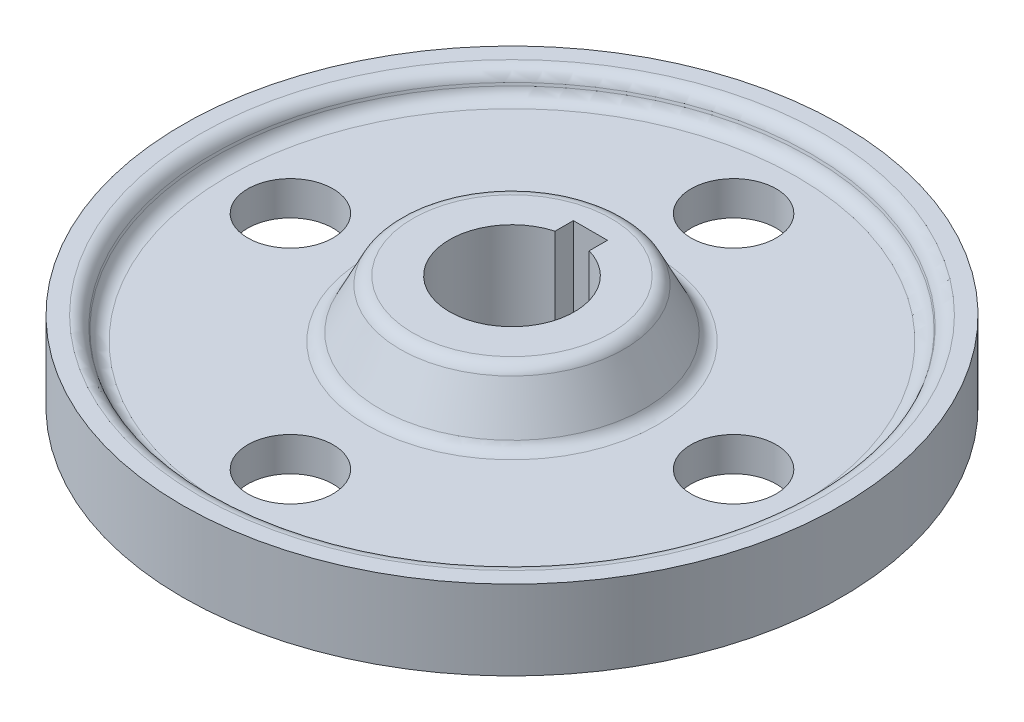
SolidWorks part; units mm, degrees
material "炭素鋼(普通)"
ref_plane "VERT" through (0, 0, 0) normal (0, 0, 1) x (1, 0, 0)
ref_plane "HOR" through (0, 0, 0) normal (0, 1, 0) x (1, 0, 0)
ref_plane "CTR" through (0, 0, 0) normal (1, 0, 0) x (0, 0, -1)
ref_axis "A_X" through (60.9, 0, 0) along (-1, 0, 0)
ref_axis "A_Y" through (0, 14.3, 0) along (0, -1, 0)
ref_axis "A_Z" through (0, 0, 63.8) along (0, 0, -1)
sketch3d "PNT_CG"
  point P0 (0, 0, 0)
sketch "Sketch1" plane through (0, 0, 0) normal (0, 1, 0) x (1, 0, 0)
  circle A0 centre (0, 0) radius 58
  dimension "D1" = 116
extrude "Boss-Extrude1" add sketch "Sketch1" along normal blind 13
sketch "Sketch3" plane through (0, 13, 0) normal (0, 1, 0) x (1, 0, 0)
  circle A0 centre (0, 0) radius 11
  dimension "D1" = 22
extrude "Cut-Extrude1" cut sketch "Sketch3" against normal through all contours A0
sketch "Sketch5" plane through (0, 13, 0) normal (0, 1, 0) x (1, 0, 0)
  circle A0 centre (0, 0) radius 39 construction
  circle A1 centre (0, 39) radius 7.5
  circle A2 centre (39, 0) radius 7.5
  circle A3 centre (0, -39) radius 7.5
  circle A4 centre (-39, 0) radius 7.5
  point P14 (0, 0)
  dimension "D1" = 78
  dimension "D2" = 4
extrude "Cut-Extrude2" cut sketch "Sketch5" against normal through all contours A1 | A4 | A3 | A2
sketch "Sketch14" plane through (0, 0, 0) normal (0, 0, 1) x (1, 0, 0)
  line L0 (-39, 25.626) -> (-39, -22.3805) construction
  line L1 (0, -14.3) -> (0, 14.3) construction
  line L2 (-52, 3) -> (-24, 3)
  line L3 (63.8, 0) -> (-63.8, 0) construction
  line L4 (-24, 3) -> (-19, 13)
  line L5 (58, 13) -> (-58, 13) construction
  line L6 (-19, 13) -> (-55, 13)
  line L7 (-52, 3) -> (-55, 13)
  line L9 (-58, 13) -> (-58, 0) construction
  dimension "D1" = 39
  dimension "D2" = 3
  dimension "D3" = 19
  dimension "D4" = 24
  dimension "D5" = 3
  dimension "D6" = 6
revolve "Cut-Revolve2" cut sketch "Sketch14" angle 360 about axis through (0, 14.3, 0) along (0, -1, 0)
sketch "Sketch15" plane through (0, 13, 0) normal (0, 1, 0) x (1, 0, 0)
  line L0 (0, -14.3) -> (0, 14.3) construction
  line L2 (3, 8.2) -> (-3, 8.2)
  line L3 (3, 8.2) -> (3, 13.8)
  line L4 (3, 13.8) -> (-3, 13.8)
  line L5 (-3, 8.2) -> (-3, 13.8)
  line L6 (3, 8.2) -> (-3, 13.8) construction
  line L7 (3, 13.8) -> (-3, 8.2) construction
  circle A0 centre (0, 0) radius 11 construction
  point P2 (0, 11)
  dimension "D1" = 5.6
  dimension "D2" = 6
extrude "Cut-Extrude5" cut sketch "Sketch15" against normal through all contours L2 L5 L4 L3
sketch "Sketch16" plane through (0, 13, 0) normal (0, 1, 0) x (1, 0, 0)
  circle A0 centre (0, 0) radius 40
  circle A1 centre (0, 0) radius 60
extrude "Cut-Extrude6" cut sketch "Sketch16" against normal blind 6
fillet "Fillet1" radius 2.5 4 edges at (0, 13, 19) (0, 3, 24) (0, 3, 52) (0, 7, 53.2)
mirror "Mirror3" about plane through (0, 0, 0) normal (0, 1, 0) of bodies 110
sketch "Sketch17" [suppressed] plane through (0, 0, 0) normal (1, 0, 0) x (0, 0, -1)
  line L0 (0, 22.5669) -> (0, -20.1914)
  line L5 (0, 22.5669) -> (65.7443, 22.5669)
  line L6 (0, -20.1914) -> (65.7443, -20.1914)
  line L7 (65.7443, 22.5669) -> (65.7443, -20.1914)
extrude "Cut-Extrude7" [suppressed] cut sketch "Sketch17" against normal through all
sketch "Sketch18" [suppressed] plane through (0, 0, 0) normal (1, 0, 0) x (0, 0, -1)
  line L0 (0, 14.3) -> (0, -14.3) construction
  line L1 (63.3551, -18.7293) -> (-63.3551, -18.7293)
  line L2 (63.3551, -18.7293) -> (63.3551, 20.4873)
  line L3 (63.3551, 20.4873) -> (-63.3551, 20.4873)
  line L4 (-63.3551, -18.7293) -> (-63.3551, 20.4873)
  line L5 (63.3551, -18.7293) -> (-63.3551, 20.4873) construction
  line L6 (63.3551, 20.4873) -> (-63.3551, -18.7293) construction
  point P0 (0, 0.879)
extrude "Cut-Extrude8" [suppressed] cut sketch "Sketch18" against normal through all contours L3 L4 L1 L2
